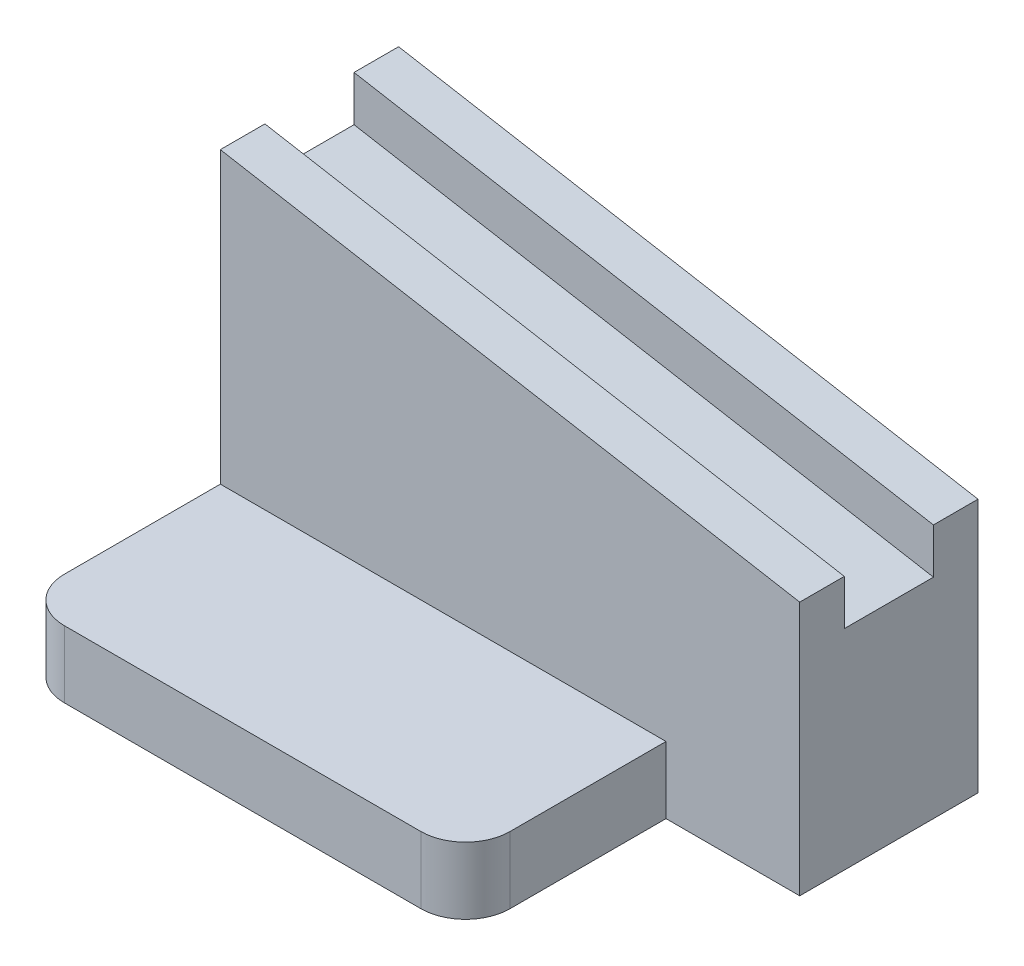
SolidWorks part; units mm, degrees
ref_plane "Plano frontal" through (0, 0, 0) normal (0, 0, 1) x (1, 0, 0)
ref_plane "Plano superior" through (0, 0, 0) normal (0, 1, 0) x (1, 0, 0)
ref_plane "Plano direito" through (0, 0, 0) normal (1, 0, 0) x (0, 0, -1)
sketch "Esboço1" plane through (0, 0, 0) normal (0, 0, 1) x (1, 0, 0)
  line L0 (-53.2953, 9.3008) -> (76.7047, 9.3008)
  line L1 (-53.2953, 9.3008) -> (-53.2953, 89.3008)
  line L2 (76.7047, 9.3008) -> (76.7047, 66.3783)
  line L3 (-53.2953, 89.3008) -> (76.7047, 66.3783)
  dimension "D1" = 100
  dimension "D2" = 80
  dimension "D3" = 130
extrude "Ressalto-extrusão1" add sketch "Esboço1" along normal blind 40
sketch "Esboço3" [suppressed] plane through (13.6643, 77.494, 0) normal (0.1736, 0.9848, 0) x (0.9848, -0.1736, 0)
  line L0 (64.0129, -40) -> (-67.9926, -40) construction
  line L1 (-71.0201, -30) -> (70.4962, -30)
  line L2 (-71.0201, -30) -> (-71.0201, -10)
  line L3 (-71.0201, -10) -> (70.4962, -10)
  line L4 (70.4962, -30) -> (70.4962, -10)
  line L5 (64.0129, 0) -> (-67.9926, 0) construction
  dimension "D1" = 10
  dimension "D2" = 10
extrude "Corte-extrusão2" [suppressed] cut sketch "Esboço3" against normal blind 10
sketch "Esboço4" plane through (13.6643, 77.494, 0) normal (0.1736, 0.9848, 0) x (0.9848, -0.1736, 0)
  line L0 (64.0129, 0) -> (-67.9926, 0) construction
  line L1 (-77.3839, -10) -> (94.2466, -10)
  line L2 (-77.3839, -10) -> (-77.3839, -30)
  line L3 (-77.3839, -30) -> (94.2466, -30)
  line L4 (94.2466, -10) -> (94.2466, -30)
  line L5 (64.0129, -40) -> (-67.9926, -40) construction
  dimension "D1" = 10
  dimension "D2" = 10
extrude "Corte-extrusão3" cut sketch "Esboço4" against normal blind 10
sketch "Esboço5" plane through (0, 0, 40) normal (0, 0, 1) x (1, 0, 0)
  line L1 (-53.2953, 9.3008) -> (46.7047, 9.3008)
  line L2 (-53.2953, 9.3008) -> (-53.2953, 24.3008)
  line L3 (-53.2953, 24.3008) -> (46.7047, 24.3008)
  line L4 (46.7047, 9.3008) -> (46.7047, 24.3008)
  dimension "D1" = 15
  dimension "D2" = 100
extrude "Ressalto-extrusão2" add sketch "Esboço5" along normal blind 45
fillet "Filete6" radius 10 1 edges at (-53.2953, 16.8008, 85) type face fillet first side face at (-53.2953, 61.52, 35.25) second side face at (-3.2953, 16.8008, 85)
fillet "Filete7" radius 10 1 edges at (46.7047, 16.8008, 85) type face fillet first side face at (1.7047, 16.8008, 85) second side face at (46.7047, 14.9258, 68.125)
